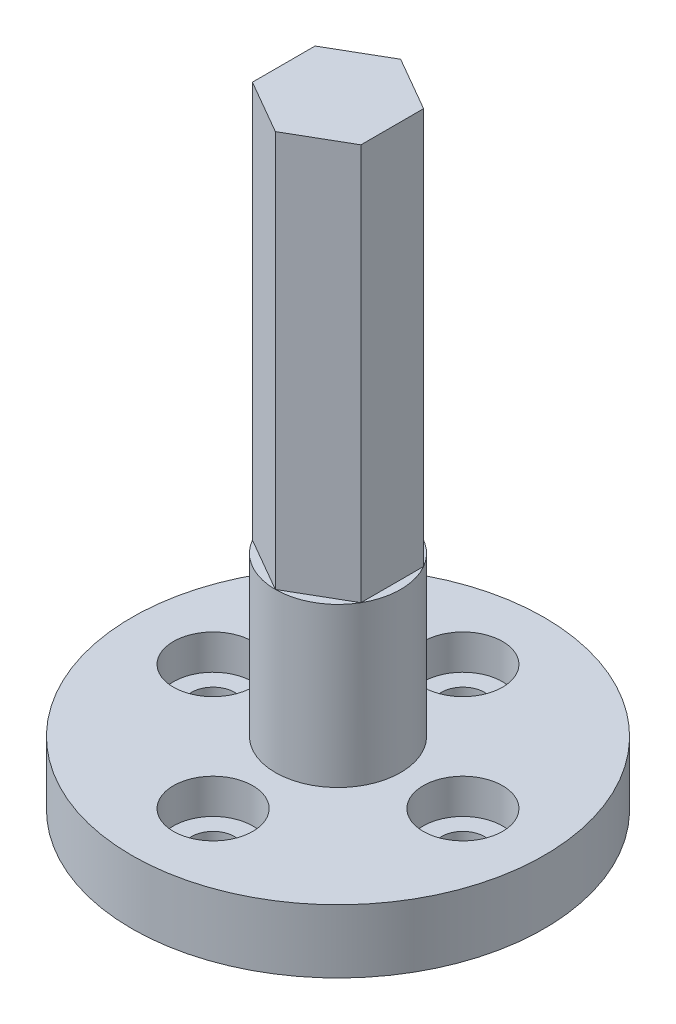
SolidWorks part; units mm, degrees
ref_plane "Alzado" through (0, 0, 0) normal (0, 0, 1) x (1, 0, 0)
ref_plane "Planta" through (0, 0, 0) normal (0, 1, 0) x (1, 0, 0)
ref_plane "Vista lateral" through (0, 0, 0) normal (1, 0, 0) x (0, 0, -1)
sketch "Croquis3" plane through (0, 0, 0) normal (0, 1, 0) x (1, 0, 0)
  circle A0 centre (0, 0) radius 13
  dimension "D1" = 26
extrude "Saliente-Extruir1" add sketch "Croquis3" along normal blind 4
sketch "Croquis4" plane through (0, 4, 0) normal (0, 1, 0) x (1, 0, 0)
  circle A0 centre (0, 0) radius 3.95
  dimension "D1" = 7.9
extrude "Saliente-Extruir2" add sketch "Croquis4" along normal blind 35
sketch "Croquis7" plane through (0, 0, 0) normal (0, -1, 0) x (1, 0, 0)
  circle A0 centre (0, 0) radius 12
  dimension "D1" = 24
sketch "Croquis12" plane through (0, 39, 0) normal (0, 1, 0) x (1, 0, 0)
  line L1 (0, 3.95) -> (-3.4208, 1.975)
  line L2 (-3.4208, 1.975) -> (-3.4208, -1.975)
  line L3 (-3.4208, -1.975) -> (0, -3.95)
  line L4 (0, -3.95) -> (3.4208, -1.975)
  line L5 (3.4208, -1.975) -> (3.4208, 1.975)
  line L6 (3.4208, 1.975) -> (0, 3.95)
  circle A0 centre (0, 0) radius 3.95 construction
  circle A1 centre (0, 0) radius 3.95 construction
  circle A2 centre (0, 0) radius 3.95 construction
extrude "Cortar-Extruir7" cut sketch "Croquis12" against normal blind 25 flip side to cut
sketch "Croquis13" plane through (0, 0, 0) normal (0, -1, 0) x (1, 0, 0)
  circle A0 centre (0, 7.875) radius 1.35
  circle A1 centre (7.875, 0) radius 1.35
  circle A2 centre (0, -7.875) radius 1.35
  circle A3 centre (-7.875, 0) radius 1.35
  point P12 (0, 0)
  dimension "D1" = 7.875
  dimension "D3" = 2.7
  dimension "D2" = 4
extrude "Cortar-Extruir8" cut sketch "Croquis13" against normal blind 10
sketch "Croquis14" plane through (0, 4, 0) normal (0, 1, 0) x (1, 0, 0)
  circle A0 centre (0, 7.875) radius 1.35 construction
  circle A1 centre (0, 7.875) radius 1.35 construction
  circle A2 centre (0, 7.875) radius 2.5
  circle A3 centre (7.875, 0) radius 2.5
  circle A4 centre (0, -7.875) radius 2.5
  circle A5 centre (-7.875, 0) radius 2.5
  point P13 (0, 0)
  dimension "D1" = 5
  dimension "D2" = 4
extrude "Cortar-Extruir9" cut sketch "Croquis14" against normal blind 2.2
